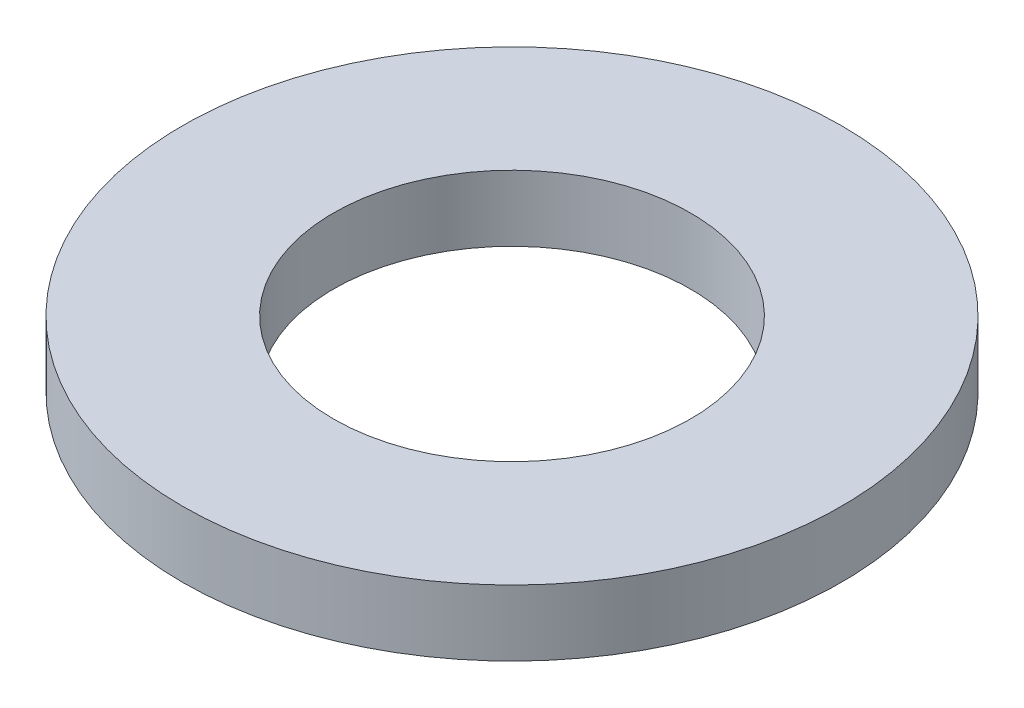
SolidWorks part; units mm, degrees
ref_plane "Front Plane" through (0, 0, 0) normal (0, 0, 1) x (1, 0, 0)
ref_plane "Top Plane" through (0, 0, 0) normal (0, 1, 0) x (1, 0, 0)
ref_plane "Right Plane" through (0, 0, 0) normal (1, 0, 0) x (0, 0, -1)
sketch "Sketch1" plane through (0, 0, 0) normal (0, 1, 0) x (1, 0, 0)
  circle A0 centre (0, 0) radius 60
  dimension "FLANGE_OD" = 120
extrude "Boss-Extrude1" add sketch "Sketch1" along normal blind 12
sketch "Sketch2" plane through (0, 0, 0) normal (0, 1, 0) x (1, 0, 0)
  circle A0 centre (0, 0) radius 32.5
  dimension "BORE_D" = 65
extrude "Cut-Extrude1" cut sketch "Sketch2" along normal through all
sketch "Sketch3" plane through (0, 12, 0) normal (0, 1, 0) x (1, 0, 0)
  circle A0 centre (0, 0) radius 22.1442 construction
  circle A1 centre (-22.1442, 0) radius 4.7529
  dimension "BOLT_D" = 9.5058
  dimension "BOLT_PCD" = 44.2884
extrude "Cut-Extrude2" cut sketch "Sketch3" against normal blind 9.2923 rebuild error yes
pattern_circular "CirPattern1" count 3 over 360 rebuild error yes
